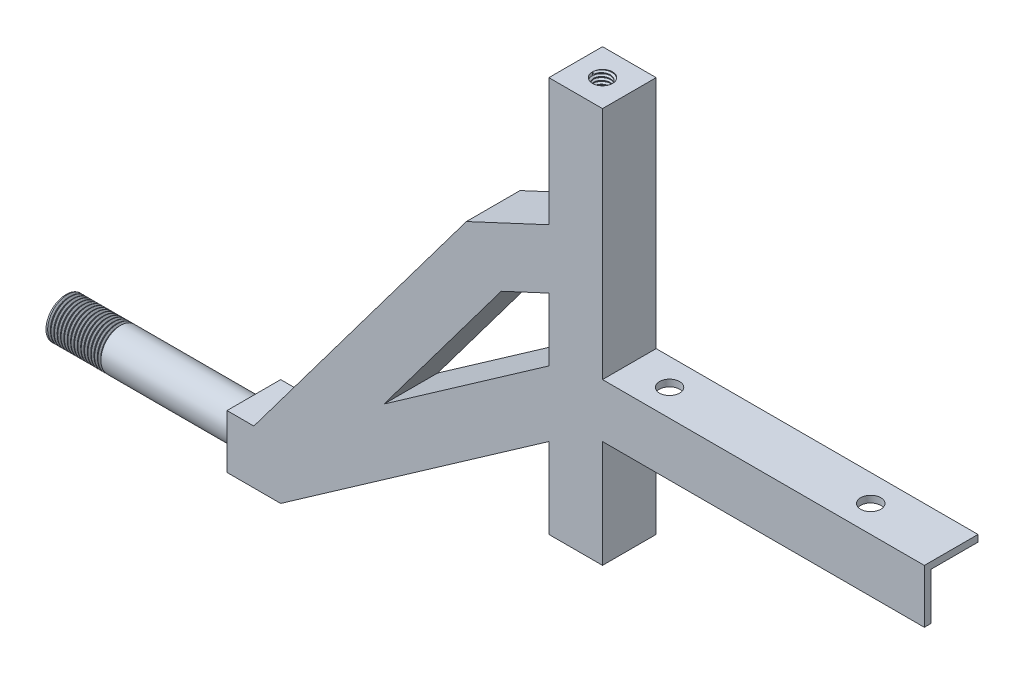
SolidWorks part; units mm, degrees
material "Plain Carbon Steel"
ref_plane "Front Plane" through (0, 0, 0) normal (0, 0, 1) x (1, 0, 0)
ref_plane "Top Plane" through (0, 0, 0) normal (0, 1, 0) x (1, 0, 0)
ref_plane "Right Plane" through (0, 0, 0) normal (1, 0, 0) x (0, 0, -1)
sketch "Sketch1" plane through (0, 0, 0) normal (0, 1, 0) x (1, 0, 0)
  line L1 (12.7, -12.7) -> (-12.7, -12.7)
  line L2 (12.7, -12.7) -> (12.7, 12.7)
  line L3 (12.7, 12.7) -> (-12.7, 12.7)
  line L4 (-12.7, -12.7) -> (-12.7, 12.7)
  line L5 (12.7, -12.7) -> (-12.7, 12.7) construction
  line L6 (12.7, 12.7) -> (-12.7, -12.7) construction
  line L7 (10.16, -10.16) -> (-10.16, -10.16)
  line L8 (10.16, -10.16) -> (10.16, 10.16)
  line L9 (10.16, 10.16) -> (-10.16, 10.16)
  line L10 (-10.16, -10.16) -> (-10.16, 10.16)
  line L11 (10.16, -10.16) -> (-10.16, 10.16) construction
  line L12 (10.16, 10.16) -> (-10.16, -10.16) construction
  point P0 (0, 0)
  point P5 (0, 0)
  dimension "D1" = 2.54
  dimension "1" = 25.4
extrude "Sq_Tb Extrude" add sketch "Sketch1" along normal blind 187.325
sketch "Sketch3" plane through (0, 187.325, 0) normal (0, 1, 0) x (1, 0, 0)
  line L1 (10.16, -10.16) -> (-10.16, -10.16)
  line L2 (10.16, -10.16) -> (10.16, 10.16)
  line L3 (10.16, 10.16) -> (-10.16, 10.16)
  line L4 (-10.16, -10.16) -> (-10.16, 10.16)
  line L5 (10.16, -10.16) -> (-10.16, 10.16) construction
  line L6 (10.16, 10.16) -> (-10.16, -10.16) construction
  circle A0 centre (0, 0) radius 4.7625
  point P0 (0, 0)
  dimension "D1" = 9.525
extrude "End Caps" add sketch "Sketch3" against normal blind 6.35
ref_plane "Mid-Plane" through (0, 93.6625, 0) normal (0, 1, 0) x (1, 0, 0)
mirror "End Cap Mirror" about plane through (0, 93.6625, 0) normal (0, 1, 0) of "End Caps"
thread "Top Thread" pitch 1.5875 method extrude profile "Thread Profile1" start angle 0, offset 0, length 0, pitch 1.5875, diameter 9.525
ref_plane "Plane2" through (-4.7625, 187.325, 0) normal (0, 0, 1) x (-1, 0, 0)
sketch "Thread Profile1" plane through (-4.7625, 187.325, 0) normal (0, 0, 1) x (-1, 0, 0)
  line L0 (0, 0) -> (0, 1.5875) construction
  line L11 (0, 0) -> (0, 1.3891)
  line L12 (0, 1.3891) -> (-0.8593, 0.893)
  line L13 (-0.8593, 0.893) -> (-0.8593, 0.4961)
  line L15 (-0.8593, 0.4961) -> (0, 0)
  line L17 (-0.8593, 0.6945) -> (0, 0.6945) construction
  point P2 (0, 0)
  dimension "Pitch" = 1.5875
  dimension "Profile_Angle" = 60
  dimension "Profile_Land" = 0.3969
  dimension "Profile_Height" = 0.8593
thread "Bottom Thread" pitch 1.5875 method extrude profile "Thread Profile2" start angle 0, offset 0, length 0, pitch 1.5875, diameter 9.525
ref_plane "Plane3" through (4.7625, 0, 0) normal (0, 0, 1) x (1, 0, 0)
sketch "Thread Profile2" plane through (4.7625, 0, 0) normal (0, 0, 1) x (1, 0, 0)
  line L0 (0, 0) -> (0, 1.5875) construction
  line L11 (0, 0) -> (0, 1.3891)
  line L12 (0, 1.3891) -> (-0.8593, 0.893)
  line L13 (-0.8593, 0.893) -> (-0.8593, 0.4961)
  line L15 (-0.8593, 0.4961) -> (0, 0)
  line L17 (-0.8593, 0.6945) -> (0, 0.6945) construction
  point P2 (0, 0)
  dimension "Pitch" = 1.5875
  dimension "Profile_Angle" = 60
  dimension "Profile_Land" = 0.3969
  dimension "Profile_Height" = 0.8593
sketch "Sketch9" plane through (0, 0, 0) normal (0, 0, 1) x (1, 0, 0)
  line L0 (-12.7, 126.996) -> (-51.7653, 108.7796)
  line L1 (-12.7, 187.325) -> (-12.7, 0) construction
  line L2 (-102.0827, 41.6898) -> (-81.7627, 26.4498) construction
  line L3 (-35.2635, 88.4487) -> (-12.7, 98.9702)
  line L4 (-12.7, 38.0909) -> (-139.7, -50.8)
  line L5 (-90.7525, 14.4633) -> (-12.7, 69.0945)
  line L6 (-12.7, 69.0945) -> (-12.7, 38.0909)
  line L8 (-51.7653, 108.7796) -> (-152.4, -25.4)
  line L9 (-12.7, 126.996) -> (-12.7, 98.9702)
  line L10 (-139.7, -50.8) -> (-35.2635, 88.4487)
  line L11 (-139.7, -50.8) -> (-165.1, -50.8)
  line L12 (-165.1, -50.8) -> (-165.1, -25.4)
  line L13 (-165.1, -25.4) -> (-152.4, -25.4)
  line L14 (-32.2327, 117.8878) -> (-21.4982, 94.8676) construction
  line L15 (-165.1, -38.1) -> (0, -38.1) construction
  line L16 (0, -38.1) -> (0, 0) construction
  line L18 (-12.7, 0) -> (12.7, 0) construction
  line L19 (-51.7262, 41.7789) -> (-37.1613, 20.9697) construction
  line L20 (-12.7, 69.0945) -> (32.9312, 3.9003) construction
  line L21 (-139.7, -50.8) -> (-114.9192, -86.2048) construction
  dimension "D3" = 172.7962
  dimension "D1" = 25.4
  dimension "D2" = 43.1038
  dimension "D4" = 65
  dimension "D5" = 12.7
  dimension "D6" = 152.4
  dimension "D7" = 115
  dimension "D8" = 25.4
  dimension "D9" = 50.8
  dimension "D10" = 55.011
  dimension "D11" = 60.329
  dimension "D12" = 38.0909
  dimension "D13" = 88.9052
extrude "Sq_Tb Angles" add sketch "Sketch9" along normal blind 12.7 and the other way blind 12.7 contours L13 L12 L11 L10 L3 L9 L0 L8 | L10 L4 L6 L5 region at (-89.8222, 35.9011, 0) region at (-64.9368, 15.7972, 0)
sketch "Sketch11" plane through (0, 0, 0) normal (0, 0, 1) x (1, 0, 0)
  line L0 (-165.1, -38.1) -> (-254, -38.1)
  line L1 (-165.1, -50.8) -> (-165.1, -25.4) construction
  line L2 (-254, -38.1) -> (-254, -28.575)
  line L3 (-254, -28.575) -> (-165.1, -28.575)
  line L6 (-165.1, -28.575) -> (-165.1, -38.1)
  dimension "D2" = 9.525
  dimension "D4" = 88.9
revolve "Wheel Rod" add sketch "Sketch11" angle 360 about L0
thread "Wheel Threads" pitch 1.5875 method cut profile "Thread Profile3" start angle 0, offset 0, length 25.4, pitch 1.5875, diameter 19.05
ref_plane "Plane4" through (-254, -38.1, -9.525) normal (0, -1, 0) x (0, 0, -1)
sketch "Thread Profile3" plane through (-254, -38.1, -9.525) normal (0, -1, 0) x (0, 0, -1)
  line L0 (0, 0) -> (0, 1.5875) construction
  line L11 (0, 0) -> (0, 1.3891)
  line L12 (0, 1.3891) -> (-0.8593, 0.893)
  line L13 (-0.8593, 0.893) -> (-0.8593, 0.4961)
  line L15 (-0.8593, 0.4961) -> (0, 0)
  line L17 (-0.8593, 0.6945) -> (0, 0.6945) construction
  point P2 (0, 0)
  dimension "Pitch" = 1.5875
  dimension "Profile_Angle" = 60
  dimension "Profile_Land" = 0.3969
  dimension "Profile_Height" = 0.8593
ref_plane "Tie-Rod Mount Plane" through (0, 34.925, 0) normal (0, 1, 0) x (1, 0, 0)
sketch "Sketch15" plane through (0, 34.925, 0) normal (0, 1, 0) x (1, 0, 0)
  line L0 (0, 12.7) -> (12.7, 25.4)
  line L1 (12.7, 12.7) -> (-12.7, 12.7) construction
  line L2 (12.7, 25.4) -> (76.2, 25.4)
  line L3 (0, -12.7) -> (12.7, -25.4)
  line L4 (-12.7, -12.7) -> (12.7, -12.7) construction
  line L5 (0, 12.7) -> (12.7, 12.7)
  line L6 (12.7, -12.7) -> (12.7, 12.7) construction
  line L7 (12.7, 12.7) -> (12.7, -12.7)
  line L8 (12.7, -12.7) -> (0, -12.7)
  line L9 (12.7, -25.4) -> (76.2, -25.4)
  line L10 (76.2, -25.4) -> (76.2, 25.4) construction
  line L11 (12.7, 25.4) -> (12.7, 12.7) construction
  line L12 (12.7, -12.7) -> (12.7, -25.4) construction
  line L13 (76.2, 25.4) -> (88.9, 12.7)
  line L14 (88.9, 12.7) -> (88.9, -12.7)
  line L15 (88.9, -12.7) -> (76.2, -25.4)
  line L16 (12.7, 0) -> (88.9, 0) construction
  dimension "D1" = 12.7
  dimension "D2" = 76.2
  dimension "D3" = 12.7
extrude "Tie-Rod Mount Plate" [suppressed] add sketch "Sketch15" along normal blind 6.35
sketch "Sketch16" [suppressed] plane through (0, 41.275, 0) normal (0, 1, 0) x (1, 0, 0)
  line L0 (12.7, 0) -> (63.5, 0) construction
  line L1 (12.7, -12.7) -> (12.7, 12.7) construction
  line L2 (63.5, 0) -> (63.5, 15.875) construction
  line L3 (12.7, 0) -> (76.2, 0) construction
  circle A0 centre (63.5, 15.875) radius 4.7625
  circle A1 centre (63.5, -15.875) radius 4.7625
  circle A2 centre (76.2, 0) radius 4.7625
  dimension "D1" = 50.8
  dimension "D3" = 9.525
  dimension "D2" = 15.875
  dimension "D4" = 63.5
extrude "Tie-Rod Mount Hole" [suppressed] cut sketch "Sketch16" against normal through all
ref_plane "Plane5" through (0, 50.8, 0) normal (0, -1, 0) x (-1, 0, 0)
sketch "Sketch17" plane through (0, 50.8, 0) normal (0, -1, 0) x (-1, 0, 0)
  line L0 (-12.7, -12.7) -> (-12.7, 12.7) construction
  line L1 (-12.7, 12.7) -> (12.7, 12.7)
  line L2 (-12.7, 12.7) -> (-12.7, 88.9)
  line L3 (-12.7, 88.9) -> (12.7, 88.9)
  line L4 (12.7, 12.7) -> (12.7, 88.9)
  line L5 (-12.7, 12.7) -> (12.7, 88.9) construction
  line L6 (-12.7, 88.9) -> (12.7, 12.7) construction
  line L7 (-12.7, 12.7) -> (12.7, 12.7) construction
  point P4 (0, 50.8)
  dimension "D1" = 25.4
  dimension "D2" = 76.2
extrude "Boss-Extrude1" [suppressed] add sketch "Sketch17" against normal blind 25.4
sketch "Sketch18" [suppressed] plane through (0, 76.2, 0) normal (0, 1, 0) x (1, 0, 0)
  line L0 (0, 0) -> (0, 63.5) construction
  circle A0 centre (0, 63.5) radius 4.7625
  dimension "D1" = 63.5
  dimension "D2" = 9.525
extrude "Cut-Extrude1" [suppressed] cut sketch "Sketch18" against normal through all
sketch "Sketch19" plane through (12.7, 0, 0) normal (1, 0, 0) x (0, 0, -1)
  line L0 (12.7, 76.2) -> (-12.7, 76.2)
  line L1 (-12.7, 187.325) -> (-12.7, 0) construction
  line L2 (-12.7, 76.2) -> (-12.7, 50.8)
  line L3 (-65.0506, 50.8) -> (65.0506, 50.8) construction
  line L4 (-12.7, 50.8) -> (-9.525, 50.8)
  line L5 (-9.525, 50.8) -> (-9.525, 73.025)
  line L6 (-9.525, 73.025) -> (12.7, 73.025)
  line L7 (12.7, 73.025) -> (12.7, 76.2)
  line L8 (-12.7, 0) -> (12.7, 0) construction
  dimension "D1" = 3.175
  dimension "D2" = 76.2
extrude "Boss-Extrude2" add sketch "Sketch19" along normal blind 152.4
sketch "Sketch20" plane through (0, 76.2, 0) normal (0, 1, 0) x (1, 0, 0)
  line L0 (88.9, -12.7) -> (88.9, 0) construction
  line L2 (165.1, -12.7) -> (12.7, -12.7) construction
  line L3 (0, 0) -> (31.75, 0) construction
  line L4 (31.75, 0) -> (127, 0) construction
  circle A0 centre (127, 0) radius 4.7625
  circle A1 centre (31.75, 0) radius 4.7625
  point P8 (88.9, 0)
  dimension "D1" = 31.75
  dimension "D2" = 9.525
  dimension "D3" = 127
extrude "Cut-Extrude2" cut sketch "Sketch20" against normal through all
